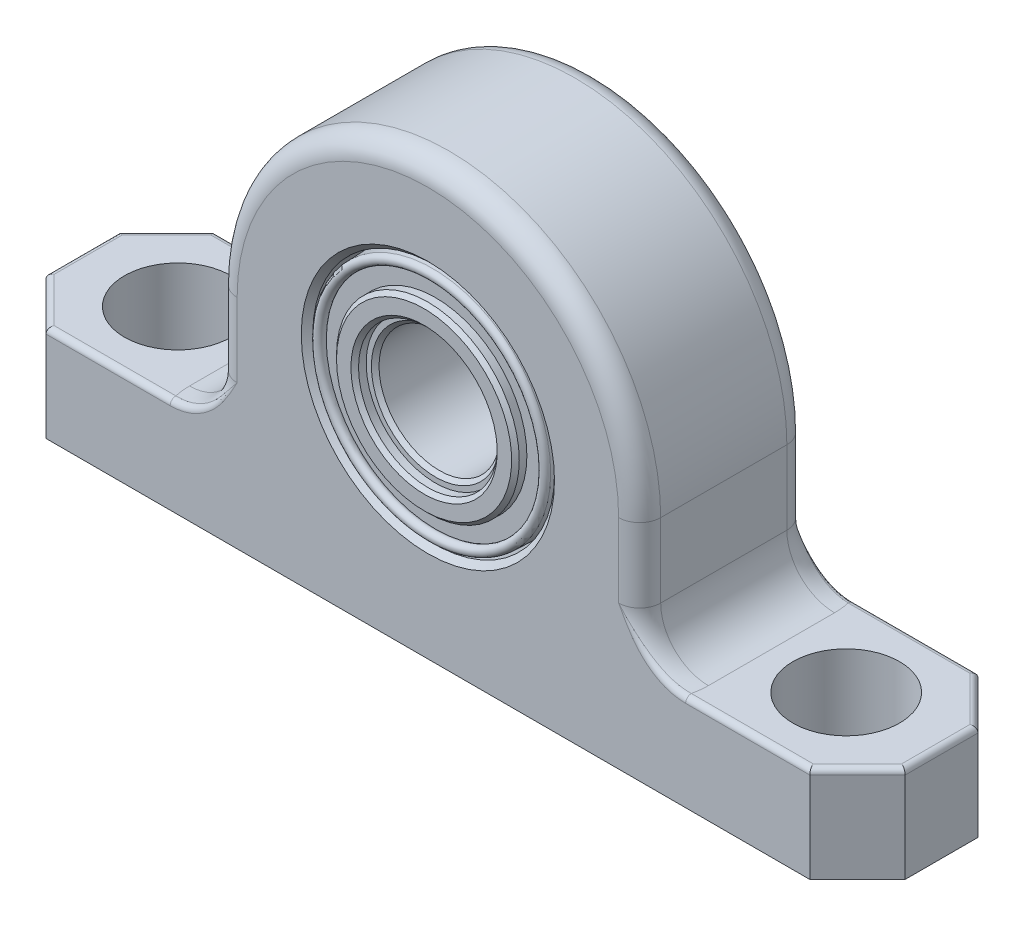
SolidWorks part; units mm, degrees
material "6061 Alloy"
ref_plane "Front Plane" through (0, 0, 0) normal (0, 0, 1) x (1, 0, 0)
ref_plane "Top Plane" through (0, 0, 0) normal (0, 1, 0) x (1, 0, 0)
ref_plane "Right Plane" through (0, 0, 0) normal (1, 0, 0) x (0, 0, -1)
sketch "Sketch1" plane through (0, 0, 0) normal (0, 0, 1) x (1, 0, 0)
  line L0 (-28.6, 0) -> (28.6, 0)
  line L1 (28.6, 0) -> (28.6, 6.4)
  line L2 (-28.6, 0) -> (-28.6, 6.4)
  line L3 (-28.6, 6.4) -> (-14.1, 6.4)
  line L4 (28.6, 6.4) -> (14.1, 6.4)
  line L5 (-14.1, 6.4) -> (-14.1, 14.5)
  line L6 (14.1, 6.4) -> (14.1, 14.5)
  line L7 (0, 0) -> (0, 28.6) construction
  line L8 (2.839, 17.339) -> (9.9702, 24.4702) construction
  circle A0 centre (0, 14.5) radius 4.015
  arc A1 (14.1, 14.5) -> (-14.1, 14.5) centre (0, 14.5) ccw
  circle A2 centre (0, 14.5) radius 8.049 construction
  point P16 (5.6915, 20.1915)
  point P17 (0, 18.515)
  point P18 (0, 22.549)
  dimension "D1" = 45
  dimension "D2" = 10.085
  dimension "D3" = 4.034
sketch "Sketch2" plane through (0, 0, 0) normal (0, 1, 0) x (1, 0, 0)
  line L0 (-22.25, 0) -> (22.25, 0) construction
  line L1 (-28.6, -5.6) -> (28.6, 5.6) construction
  line L2 (-28.6, 5.6) -> (28.6, 5.6)
  line L3 (-28.6, 5.6) -> (-28.6, -5.6)
  line L4 (-28.6, -5.6) -> (28.6, -5.6)
  line L5 (28.6, 5.6) -> (28.6, -5.6)
  circle A0 centre (-22.25, 0) radius 3.55
  circle A1 centre (22.25, 0) radius 3.55
sketch "Sketch3" plane through (0, 0, 0) normal (0, 0, 1) x (1, 0, 0)
  line L0 (-28.6, 0) -> (-28.6, 6.4) construction
  line L1 (-28.6, 0) -> (28.6, 0) construction
  line L2 (-28.6, 6.4) -> (-14.1, 6.4) construction
  line L3 (28.6, 6.4) -> (14.1, 6.4) construction
  line L4 (28.6, 0) -> (28.6, 6.4) construction
  line L5 (14.1, 6.4) -> (14.1, 14.5) construction
  line L6 (-14.1, 6.4) -> (-14.1, 14.5) construction
  line L7 (-28.6, 0) -> (-28.6, 6.4)
  line L8 (-28.6, 0) -> (28.6, 0)
  line L9 (-28.6, 6.4) -> (-14.1, 6.4)
  line L10 (28.6, 6.4) -> (14.1, 6.4)
  line L11 (28.6, 0) -> (28.6, 6.4)
  line L12 (14.1, 6.4) -> (14.1, 14.5)
  line L13 (-14.1, 6.4) -> (-14.1, 14.5)
  arc A0 (14.1, 14.5) -> (-14.1, 14.5) centre (0, 14.5) ccw construction
  circle A1 centre (0, 14.5) radius 8.049 construction
  arc A2 (14.1, 14.5) -> (-14.1, 14.5) centre (0, 14.5) ccw
  circle A3 centre (0, 14.5) radius 8.049
extrude "Boss-Extrude1" add sketch "Sketch3" against normal up to vertex (5.6 mm away) and the other way up to vertex (5.6 mm away) up to point (-28.6, 0, -5.6) other way up to point (-28.6, 0, 5.6)
sketch "Sketch4" plane through (0, 0, 0) normal (0, 1, 0) x (1, 0, 0)
  circle A0 centre (-22.25, 0) radius 3.55 construction
  circle A1 centre (22.25, 0) radius 3.55 construction
  circle A2 centre (-22.25, 0) radius 3.55
  circle A3 centre (22.25, 0) radius 3.55
extrude "Cut-Extrude1" cut sketch "Sketch4" along normal through all
chamfer "Chamfer1" distance 3.175 angle 45 4 edges at (-28.6, 3.2, -5.6) (28.6, 3.2, 5.6) (28.6, 3.2, -5.6) (-28.6, 3.2, 5.6)
fillet "Fillet1" radius 1.4 6 edges at (-14.1, 10.45, -5.6) (0, 28.6, -5.6) (-14.1, 10.45, 5.6) (0, 28.6, 5.6) (14.1, 10.45, -5.6) (14.1, 10.45, 5.6)
fillet "Fillet2" radius 3.175 6 edges at (-13.6899, 6.4, -5.1899) (-13.6899, 6.4, 5.1899) (13.6899, 6.4, -5.1899) (13.6899, 6.4, 5.1899) (-14.1, 6.4, 0) (14.1, 6.4, 0)
chamfer "Chamfer2" distance 0.381 angle 45 2 edges at (8.049, 14.5, 5.6) (8.049, 14.5, -5.6)
fillet "Fillet3" radius 0.381 14 edges at (-14.8171, 7.1395, -5.6) (-14.8171, 7.1395, 5.6) (14.8171, 7.1395, -5.6) (14.8171, 7.1395, 5.6) (-21.2403, 6.4, -5.6) (-27.0125, 6.4, -4.0125) (-28.6, 6.4, 0) (-27.0125, 6.4, 4.0125) (-21.2403, 6.4, 5.6) (21.2403, 6.4, -5.6) (27.0125, 6.4, -4.0125) (28.6, 6.4, 0) (27.0125, 6.4, 4.0125) (21.2403, 6.4, 5.6)
sketch "Sketch5" plane through (0, 0, 0) normal (1, 0, 0) x (0, 0, -1)
  line L1 (-5.6, 22.549) -> (5.6, 22.549)
  line L2 (-5.6, 22.549) -> (-5.6, 18.515)
  line L3 (-5.6, 18.515) -> (5.6, 18.515)
  line L4 (5.6, 22.549) -> (5.6, 18.515)
sketch "Sketch6" plane through (0, 0, 0) normal (1, 0, 0) x (0, 0, -1)
  line L0 (0, 22.549) -> (5.6, 22.549)
  line L2 (0, 22.549) -> (-5.2869, 22.3644)
  line L3 (-5.6, 22.549) -> (-5.6, 18.515) construction
  line L4 (-5.092, 21.7728) -> (-5.092, 20.5842)
  line L5 (-5.092, 20.5842) -> (-5.854, 20.5842)
  line L6 (-5.854, 20.5842) -> (-5.854, 19.1173)
  line L7 (-5.854, 19.1173) -> (-5.092, 19.1173)
  line L8 (-5.092, 19.1173) -> (-5.092, 18.515)
  line L9 (-5.6, 18.515) -> (5.6, 18.515) construction
  line L10 (-5.092, 18.515) -> (3.568, 18.515)
  line L11 (5.6, 22.549) -> (5.6, 21.7728)
  line L12 (5.6, 22.549) -> (5.6, 18.515) construction
  line L13 (5.6, 21.7728) -> (1.79, 21.7728)
  line L14 (1.79, 21.7728) -> (1.79, 20.5842)
  line L15 (1.79, 20.5842) -> (4.33, 20.5842)
  line L16 (4.33, 20.5842) -> (4.33, 19.1173)
  line L17 (4.33, 19.1173) -> (3.568, 19.1173)
  line L18 (3.568, 19.1173) -> (3.568, 18.515)
  line L20 (-5.6, 14.5) -> (5.6, 14.5) construction
  line L21 (-5.6, 0) -> (-5.6, 6.019) construction
  arc A0 (-5.2869, 22.3644) -> (-5.092, 21.7728) centre (-5.2756, 22.0402) ccw
  dimension "D8" = 0.3244
  dimension "D1" = 2
  dimension "D2" = 0.254
  dimension "D3" = 0.762
  dimension "D4" = 4.034
  dimension "D5" = 1.27
  dimension "D6" = 2.54
  dimension "D7" = 1.4669
  dimension "D9" = 9.2345
revolve "Revolve1" add sketch "Sketch6" angle 360 about L20
chamfer "Chamfer3" distance 0.254 angle 45 6 edges at (4.6173, 14.5, -4.33) (6.0842, 14.5, -4.33) (4.015, 14.5, 5.092) (4.015, 14.5, -3.568) (6.0842, 14.5, 5.854) (4.6173, 14.5, 5.854)
ref_axis "Center Axis 1" through (0, 14.5, -3.314) along (0, 0, 1)
ref_plane "Contact Plane 1" through (0, 0, 0) normal (0, -1, 0) x (-1, 0, 0)
equation "\"D3@Sketch1\"=\"D2@Sketch1\"/2.50"
equation "\"D1@Fillet1\"=\"Overall Width@Sketch2\"/8"
equation "\"D7@Sketch6\"=\"D4@Sketch6\"/2.750"
equation "\"D9@Sketch6\"=\"ID@Sketch1\"*1.15"
